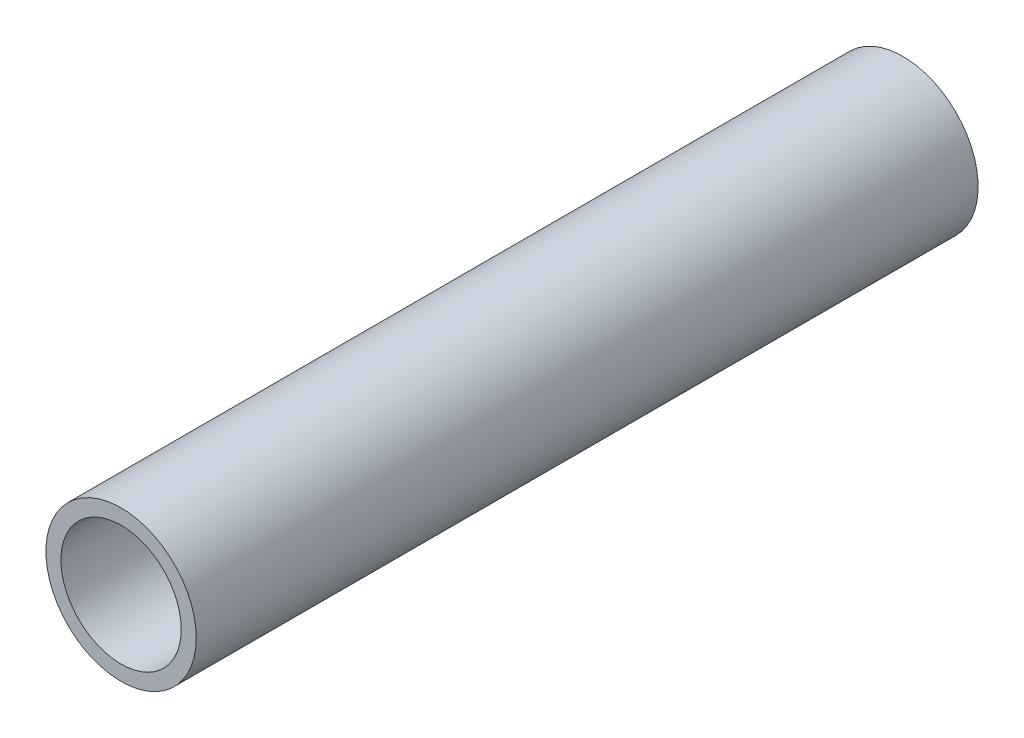
SolidWorks part; units mm, degrees
ref_plane "Plano frontal" through (0, 0, 0) normal (0, 0, 1) x (1, 0, 0)
ref_plane "Plano superior" through (0, 0, 0) normal (0, 1, 0) x (1, 0, 0)
ref_plane "Plano direito" through (0, 0, 0) normal (1, 0, 0) x (0, 0, -1)
sketch "Esboço1" plane through (0, 0, 0) normal (0, 0, 1) x (1, 0, 0)
  circle A0 centre (0, 0) radius 12.5
  circle A1 centre (0, 0) radius 10
  dimension "D1" = 25
  dimension "D2" = 20
extrude "Ressalto-extrusão1" add sketch "Esboço1" along normal blind 130
sketch "Esboço2" plane through (0, 0, 0) normal (1, 0, 0) x (0, 0, -1)
  line L0 (0, -12.5) -> (0, 12.5) construction
  circle A0 centre (5, 0) radius 12.5
  circle A1 centre (5, 0) radius 12
  dimension "D1" = 24
  dimension "D2" = 25
  dimension "D3" = 5
extrude "Corte-extrusão1" cut sketch "Esboço2" against normal blind 5 and the other way blind 5
